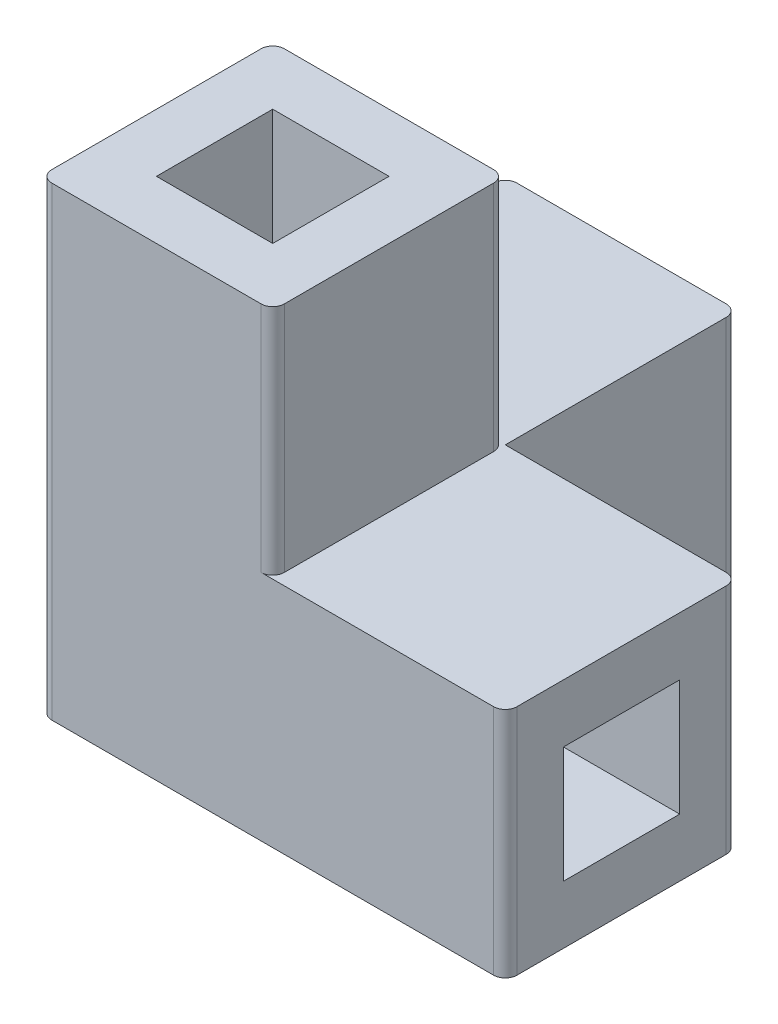
SolidWorks part; units mm, degrees
material "ABS"
ref_plane "Alzado" through (0, 0, 0) normal (0, 0, 1) x (1, 0, 0)
ref_plane "Planta" through (0, 0, 0) normal (0, 1, 0) x (1, 0, 0)
ref_plane "Vista lateral" through (0, 0, 0) normal (1, 0, 0) x (0, 0, -1)
sketch "Croquis1" plane through (0, 0, 0) normal (0, 1, 0) x (1, 0, 0)
  line L5 (0, 0) -> (80, 0)
  line L6 (0, 0) -> (0, 80)
  line L7 (0, 80) -> (80, 80)
  line L8 (80, 0) -> (80, 80)
  line L9 (80, 80) -> (40, 80)
  line L10 (80, 80) -> (80, 40)
  line L11 (80, 40) -> (40, 40)
  line L12 (40, 80) -> (40, 40)
  dimension "D1" = 80
  dimension "D2" = 80
  dimension "D3" = 40
  dimension "D4" = 40
extrude "Saliente-Extruir1" add sketch "Croquis1" along normal blind 80 contours L12 L7 L6 L5 L8 L11 region at (33.3333, 0, -33.3333)
sketch "Croquis2" plane through (0, 0, 0) normal (0, 0, 1) x (1, 0, 0)
  line L1 (80, 80) -> (40, 80)
  line L2 (80, 80) -> (80, 40)
  line L3 (80, 40) -> (40, 40)
  line L4 (40, 80) -> (40, 40)
  dimension "D1" = 40
  dimension "D2" = 40
extrude "Cortar-Extruir1" cut sketch "Croquis2" against normal blind 80
sketch "Croquis3" plane through (40, 0, 0) normal (1, 0, 0) x (0, 0, -1)
  line L1 (40, 40) -> (80, 40)
  line L2 (40, 40) -> (40, 80)
  line L3 (40, 80) -> (80, 80)
  line L4 (80, 40) -> (80, 80)
extrude "Cortar-Extruir2" cut sketch "Croquis3" against normal blind 80
fillet "Redondeo1" radius 2 8 edges at (40, 20, -80) (0, 20, -80) (0, 60, -40) (80, 20, 0) (80, 20, -40) (40, 60, 0) (40, 60, -40) (0, 40, 0)
sketch "Croquis4" plane through (0, 80, 0) normal (0, 1, 0) x (1, 0, 0)
  line L0 (0, 2) -> (0, 38) construction
  line L1 (10, 30) -> (30, 30)
  line L2 (10, 30) -> (10, 10)
  line L3 (10, 10) -> (30, 10)
  line L4 (30, 30) -> (30, 10)
  line L5 (2, 0) -> (38, 0) construction
  point P6 (0, 20)
  point P7 (10, 20)
  point P10 (20, 0)
  point P11 (20, 10)
  dimension "D1" = 20
  dimension "D2" = 20
extrude "Cortar-Extruir3" cut sketch "Croquis4" against normal blind 80
sketch "Croquis5" plane through (0, 0, -80) normal (0, 0, -1) x (-1, 0, 0)
  line L0 (-38, 40) -> (-38, 0) construction
  line L1 (-30, 30) -> (-10, 30)
  line L2 (-30, 30) -> (-30, 10)
  line L3 (-30, 10) -> (-10, 10)
  line L4 (-10, 30) -> (-10, 10)
  line L5 (-2, 40) -> (-38, 40) construction
  point P6 (-38, 20)
  point P7 (-30, 20)
  point P10 (-20, 40)
  point P11 (-20, 30)
  dimension "D1" = 20
  dimension "D2" = 20
extrude "Cortar-Extruir4" cut sketch "Croquis5" against normal up to vertex (70 mm away) up to point (30, 80, -10)
sketch "Croquis6" plane through (80, 0, 0) normal (1, 0, 0) x (0, 0, -1)
  line L0 (10, 0) -> (10, 80) construction
  line L1 (30, 30) -> (10, 30)
  line L2 (30, 30) -> (30, 10)
  line L3 (30, 10) -> (10, 10)
  line L4 (10, 30) -> (10, 10)
  line L5 (30, 10) -> (80, 10) construction
  point P7 (0, 0)
extrude "Cortar-Extruir5" cut sketch "Croquis6" against normal up to vertex (70 mm away) up to point (10, 80, -30)
